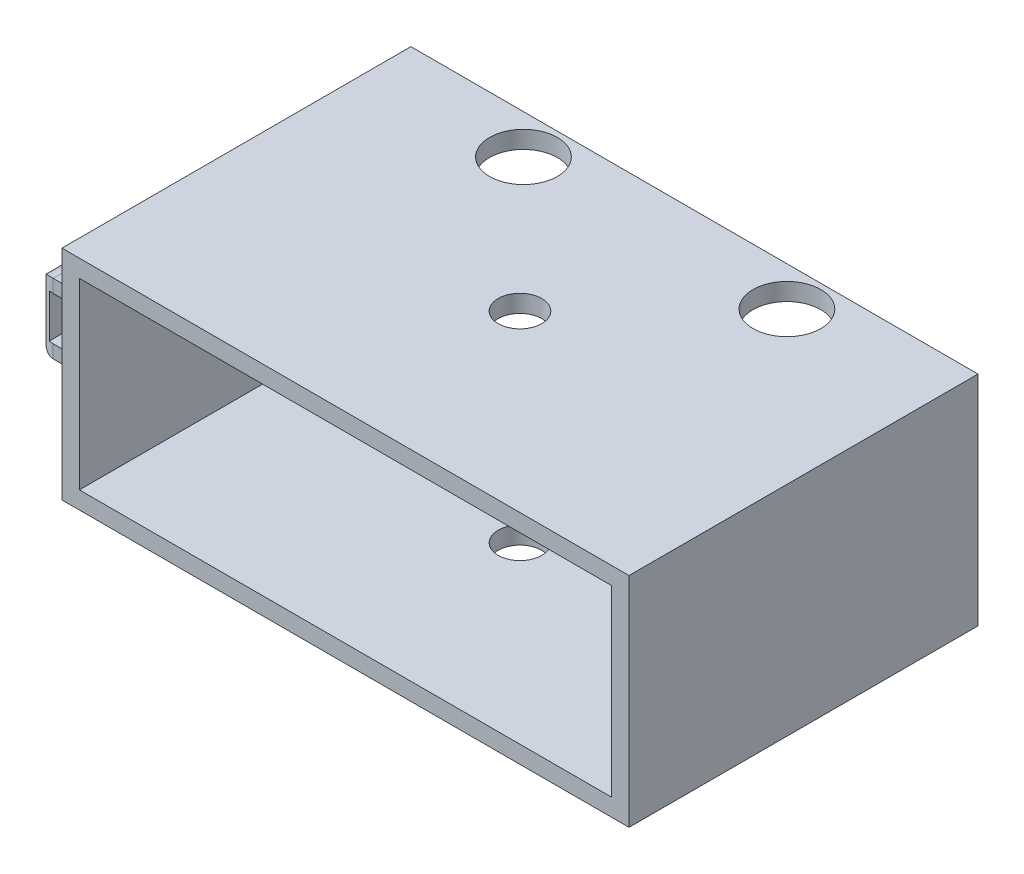
SolidWorks part; units mm, degrees
ref_plane "Front Plane" through (0, 0, 0) normal (0, 0, 1) x (1, 0, 0)
ref_plane "Top Plane" through (0, 0, 0) normal (0, 1, 0) x (1, 0, 0)
ref_plane "Right Plane" through (0, 0, 0) normal (1, 0, 0) x (0, 0, -1)
sketch "Sketch1" plane through (0, 0, 0) normal (0, 1, 0) x (1, 0, 0)
  line L1 (0, 0) -> (65, 0)
  line L2 (0, 0) -> (0, -40)
  line L3 (0, -40) -> (65, -40)
  line L4 (65, 0) -> (65, -40)
  dimension "D1" = 65
  dimension "D2" = 40
extrude "Boss-Extrude1" add sketch "Sketch1" along normal blind 25
sketch "Sketch8" plane through (0, 0, 0) normal (0, 0, -1) x (-1, 0, 0)
  line L0 (-32.5, 25) -> (-32.5, 0) construction
  line L1 (-65, 25) -> (0, 25) construction
  line L2 (-65, 0) -> (0, 0) construction
  line L4 (-63, 2) -> (-2, 2)
  line L5 (-63, 2) -> (-63, 23)
  line L6 (-63, 23) -> (-2, 23)
  line L7 (-2, 2) -> (-2, 23)
  line L8 (-63, 2) -> (-2, 23) construction
  line L9 (-63, 23) -> (-2, 2) construction
  point P6 (-32.5, 12.5)
  dimension "D1" = 21
  dimension "D2" = 61
extrude "Cut-Extrude1" cut sketch "Sketch8" against normal blind 40
sketch "Sketch9" plane through (0, 25, 0) normal (0, 1, 0) x (1, 0, 0)
  line L0 (32.5, 0) -> (32.5, -20) construction
  line L2 (65, 0) -> (0, 0) construction
  circle A1 centre (32.5, -20) radius 2.5
extrude "Cut-Extrude2" cut sketch "Sketch9" against normal blind 30
sketch "Sketch10" plane through (0, 0, 0) normal (0, -1, 0) x (1, 0, 0)
  line L0 (32.5, 40) -> (32.5, 0) construction
  line L1 (0, 40) -> (65, 40) construction
  line L2 (65, 0) -> (0, 0) construction
  circle A0 centre (17.4, 4.5) radius 3.8814
  circle A1 centre (47.6, 4.5) radius 3.8814
extrude "Cut-Extrude3" cut sketch "Sketch10" against normal blind 26
sketch "Sketch11" plane through (0, 0, 0) normal (-1, 0, 0) x (0, 0, 1)
  line L0 (0, 25) -> (40, 25) construction
  line L1 (5, 16.5) -> (13, 16.5)
  line L2 (5, 16.5) -> (5, 8.5)
  line L3 (5, 8.5) -> (13, 8.5)
  line L4 (13, 16.5) -> (13, 8.5)
  line L5 (27, 16.5) -> (35, 16.5)
  line L6 (27, 16.5) -> (27, 8.5)
  line L7 (27, 8.5) -> (35, 8.5)
  line L8 (35, 16.5) -> (35, 8.5)
  line L9 (0, 25) -> (0, 0) construction
  line L10 (40, 25) -> (40, 0) construction
  dimension "D1" = 8
  dimension "D2" = 8.5
  dimension "D3" = 8.5
  dimension "D4" = 5
  dimension "D5" = 5
extrude "Boss-Extrude2" add sketch "Sketch11" along normal blind 8
sketch "Sketch12" plane through (0, 0, 5) normal (0, 0, -1) x (-1, 0, 0)
  line L0 (8, 16.5) -> (8, 8.5) construction
  line L1 (1.5, 15) -> (6.5, 15)
  line L2 (1.5, 15) -> (1.5, 10)
  line L3 (1.5, 10) -> (6.5, 10)
  line L4 (6.5, 15) -> (6.5, 10)
  line L5 (8, 16.5) -> (0, 16.5) construction
  dimension "D1" = 5
  dimension "D2" = 1.5
  dimension "D3" = 1.5
extrude "Cut-Extrude4" cut sketch "Sketch12" against normal blind 52
fillet "Fillet1" radius 2 4 edges at (0, 8.5, 9) (0, 8.5, 31) (0, 16.5, 31) (0, 16.5, 9)
fillet "Fillet2" radius 5 4 edges at (0, 12.5, 35) (0, 12.5, 27) (0, 12.5, 5) (0, 12.5, 13)
fillet "Fillet3" radius 2 8 edges at (-8, 16.5, 31) (-8, 12.5, 35) (-8, 8.5, 31) (-8, 12.5, 27) (-8, 16.5, 9) (-8, 12.5, 13) (-8, 8.5, 9) (-8, 12.5, 5)
